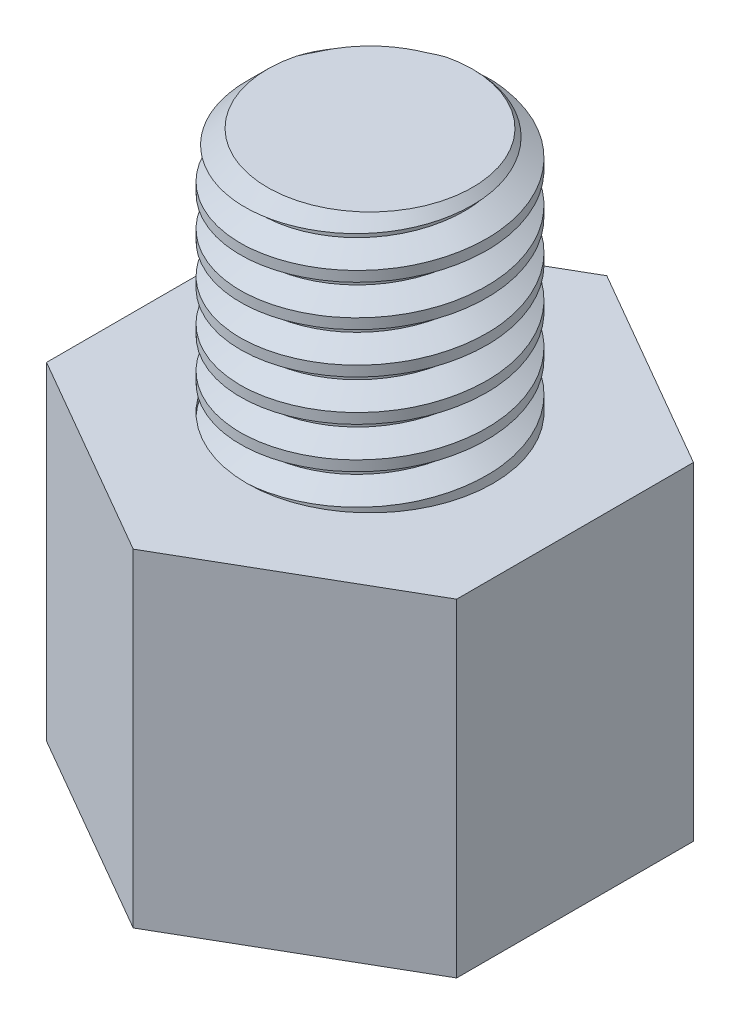
SolidWorks part; units mm, degrees
material "Tin Bearing Bronze"
ref_plane "Front Plane" through (0, 0, 0) normal (0, 0, 1) x (1, 0, 0)
ref_plane "Top Plane" through (0, 0, 0) normal (0, 1, 0) x (1, 0, 0)
ref_plane "Right Plane" through (0, 0, 0) normal (1, 0, 0) x (0, 0, -1)
sketch "Sketch2" plane through (0, 0, 0) normal (0, 1, 0) x (1, 0, 0)
  line L0 (0, 2.8868) -> (-2.5, 1.4434)
  line L1 (-2.5, 1.4434) -> (-2.5, -1.4434)
  line L2 (-2.5, -1.4434) -> (0, -2.8868)
  line L3 (0, -2.8868) -> (2.5, -1.4434)
  line L4 (2.5, -1.4434) -> (2.5, 1.4434)
  line L5 (2.5, 1.4434) -> (0, 2.8868)
  line L6 (0, -2.8868) -> (2.5, 1.4434)
  line L7 (2.5, -1.4434) -> (0, 2.8868)
  line L8 (-2.5, 1.4434) -> (2.5, 1.4434)
  line L9 (-2.5, -1.4434) -> (2.5, 1.4434) construction
  point P0 (0, 0)
  dimension "D1" = 5
extrude "Boss-Extrude1" add sketch "Sketch2" along normal blind 4 contours L9 L2 L6 L7 | L1 L9 L7 L8 | L0 L8 L7 | L7 L8 L5 | L7 L9 L8 | L9 L7 L6 | L7 L4 L6 | L3 L7 L6 region at (-0.5556, 0, -1.9245) region at (1.1111, 0, -1.9245) region at (-1.048, 0, -0.4155) region at (2.2222, 0, 0) region at (1.5278, 0, -1.2028) region at (1.8056, 0, -0.7217) region at (-0.1641, 0, 1.1153) region at (1.3889, 0, 1.4434)
sketch "Sketch3" plane through (0, 4, 0) normal (0, 1, 0) x (1, 0, 0)
  circle A0 centre (0, 0) radius 1.5
  dimension "D1" = 3
extrude "Boss-Extrude2" add sketch "Sketch3" along normal blind 3
hole_wizard "M3x0.5 Tapped Hole1" positions "Sketch8" profile "Sketch7" tap size "M3x0.5" standard "ANSI Metric"
sketch "Sketch8" plane through (0, 0, 0) normal (0, -1, 0) x (-1, 0, 0)
  point P0 (0, 0)
sketch "Sketch7" plane through (0, 0, 0) normal (1, 0, 0) x (0, 0, -1)
  line L0 (0, 0) -> (0, 4.2511)
  line L1 (0, 4.2511) -> (1.25, 3.5)
  line L2 (1.25, 3.5) -> (1.25, 0)
  line L5 (1.25, 0) -> (0, 0)
  line L10 (0, 4.2511) -> (-1.25, 3.5) construction
  line L11 (0, -6.35) -> (0, 107.95) construction
  dimension "Tap Drill Dia." = 2.5
  dimension "Tap Drill Depth" = 3.5
  dimension "Drill Angle" = 118
cosmetic thread "Hole Thread1" parameters "D1"=3.5, "D2"=3
chamfer "Chamfer1" distance 0.25 angle 45 1 edges at (0, 7, 1.5)
thread "Thread1" pitch 0.5 method cut profile "Thread Profile1" start angle 0, offset 1, length 3.5, pitch 0.5, diameter 3
ref_plane "Plane1" through (-1.5, 7.75, 0) normal (0, 0, -1) x (1, 0, 0)
sketch "Thread Profile1" plane through (-1.5, 7.75, 0) normal (0, 0, -1) x (1, 0, 0)
  line L0 (0, 0) -> (0, 0.5) construction
  line L1 (0, 0) -> (0.2706, 0.1562)
  line L2 (0.2706, 0.1562) -> (0.2706, 0.2187)
  line L3 (0.2706, 0.2187) -> (0, 0.375)
  line L4 (0.2706, 0.1875) -> (0, 0.1875) construction
  line L11 (0, 0) -> (0, 0.375)
  point P2 (0, 0)
  dimension "Pitch" = 0.5
  dimension "Profile_Angle" = 60
  dimension "Profile_Land" = 0.0625
  dimension "Profile_Height" = 0.2706
